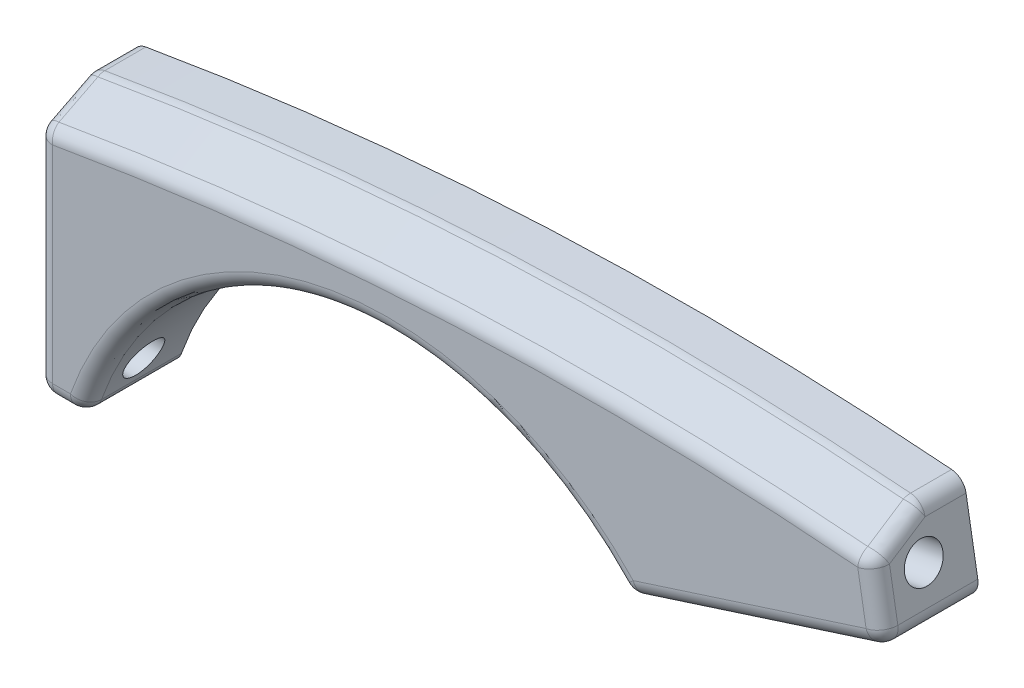
SolidWorks part; units mm, degrees
ref_plane "Front Plane" through (0, 0, 0) normal (0, 0, 1) x (1, 0, 0)
ref_plane "Top Plane" through (0, 0, 0) normal (0, 1, 0) x (1, 0, 0)
ref_plane "Right Plane" through (0, 0, 0) normal (1, 0, 0) x (0, 0, -1)
sketch "Sketch1" plane through (0, 0, 0) normal (0, 0, 1) x (1, 0, 0)
  line L0 (0, 0) -> (0, -25.4)
  line L2 (82.55, 3.81) -> (84.1536, -5.579)
  line L3 (0, -25.4) -> (4.5043, -25.4)
  line L4 (244.467, -237.1135) -> (141.8498, -254.6403) construction
  line L5 (84.1536, -5.579) -> (58.7536, -13.751)
  arc A1 (0, 0) -> (82.55, 3.81) centre (55.7888, -312.5602) cw
  circle A2 centre (34.925, -34.925) radius 31.877 construction
  arc A3 (4.5043, -25.4) -> (58.7536, -13.751) centre (34.925, -34.925) cw
  dimension "D1" = 31.877
  dimension "D2" = 317.5
  dimension "D3" = 82.55
  dimension "D4" = 25.4
  dimension "D5" = 9.525
  dimension "D6" = 25.4
  dimension "D7" = 3.81
extrude "Boss-Extrude1" add sketch "Sketch1" along normal blind 9.525
chamfer "Chamfer1" distance 5.08 distance2 2.54 1 edges at (41.1505, 4.6022, 9.525) first distance on face at (41.2128, 3.2536, 4.7625)
sketch "Sketch2" plane through (80.8424, 13.8077, 0) normal (0.9857, 0.1684, 0) x (0, 0, -1)
  circle A0 centre (-4.7625, -14.7218) radius 1.905
  arc A1 (-6.8625, -14.7218) -> (-2.6625, -14.7218) centre (-4.7625, -14.7218) ccw construction
  dimension "D1" = 3.81
extrude "Cut-Extrude1" cut sketch "Sketch2" against normal blind 12.7
sketch "Sketch3" plane through (0, 0, 0) normal (-1, 0, 0) x (0, 0, 1)
  line L0 (4.7625, -12.2986) -> (4.7625, -0.1613) construction
  line L1 (-94.3733, -75.7024) -> (9.0275, -32.1652) construction
  line L3 (4.7625, -21.8236) -> (4.7625, -33.961) construction
  line L5 (0, 0) -> (0, -25.4) construction
  circle A0 centre (4.7625, -12.2986) radius 1.905
  circle A1 centre (4.7625, -21.8236) radius 1.905
  spline S0 degree 3 poles (9.525, -2.5805) (7.8317, -1.7202) (6.1384, -0.8601) (4.445, 0) knots 0 0 0 0 0.005698 0.005698 0.005698 0.005698 construction
  dimension "D3" = 3.81
  dimension "D1" = 9.525
  dimension "D2" = 4.7625
extrude "Cut-Extrude2" cut sketch "Sketch3" against normal blind 9.525
fillet "Fillet1" radius 1.5875 15 edges at (71.4536, -9.665, 9.525) (28.2326, -3.7584, 9.525) (2.2522, -25.4, 9.525) (0, -13.9902, 9.525) (83.5727, -2.1781, 9.525) (41.37, 2.0696, 9.525) (41.1505, 4.6022, 4.445) (58.7536, -13.751, 4.7625) (4.5043, -25.4, 4.7625) (0, 0, 2.2225) (0, -25.4, 4.7625) (84.1536, -5.579, 4.7625) (82.55, 3.81, 2.2225)
